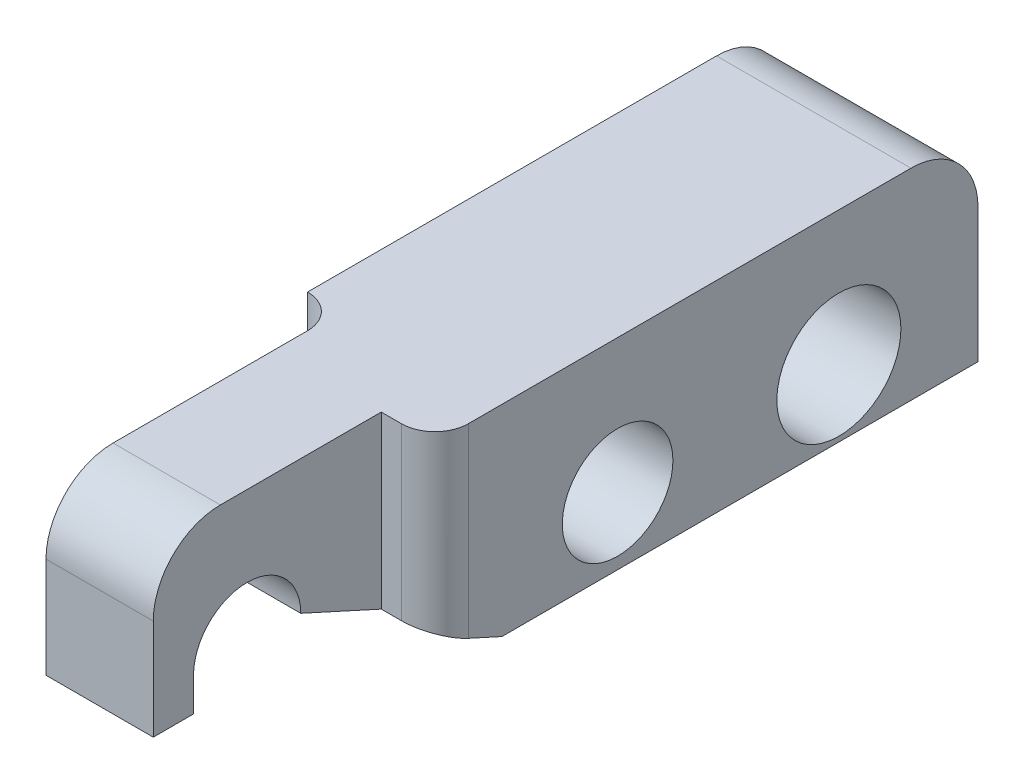
SolidWorks part; units mm, degrees
note: The reader was unsure of these and kept them because the rebuilt part matched: shared geometry of "草图1<11>".
ref_plane "前视基准面" through (0, 0, 0) normal (0, 0, 1) x (1, 0, 0)
ref_plane "上视基准面" through (0, 0, 0) normal (0, 1, 0) x (1, 0, 0)
ref_plane "右视基准面" through (0, 0, 0) normal (1, 0, 0) x (0, 0, -1)
other "Configuration Table"
sketch "草图1" plane through (0, 0, 0) normal (1, 0, 0) x (0, 0, -1)
  line L0 (-9.425, 0) -> (2.075, 0)
  line L21 (-9.425, 1) -> (2.075, 1)
  line L22 (-9.425, 1) -> (-9.425, -2)
  line L23 (-9.425, -2) -> (2.075, -2)
  line L24 (2.075, 1) -> (2.075, -2)
  line L25 (-8.825, 5.2785) -> (-8.825, 3.4146)
  line L26 (-0.925, 5.2633) -> (-0.925, 3.6744)
  line L27 (-7.225, 1) -> (-7.225, -2)
  line L28 (-7.225, 0) -> (-5.025, 1)
  line L29 (-9.425, 0.5) -> (-8.825, 0.5)
  line L30 (-9.425, 0.5) -> (-9.425, 0)
  line L31 (-9.425, 0) -> (-8.825, 0)
  line L32 (-8.825, 0.5) -> (-8.825, 0)
  line L33 (-5.025, 1) -> (-5.025, 0)
  circle A0 centre (0, 0) radius 0.925
  circle A1 centre (-3.3, 0) radius 0.825
  circle A2 centre (-8.025, 0) radius 0.8
  dimension "D1" = 1.85
  dimension "D2" = 1.65
  dimension "D9" = 1.6
  dimension "D3" = 3.3
  dimension "D4" = 3
  dimension "D5" = 11.5
  dimension "D6" = 0.6
  dimension "D7" = 3
  dimension "D8" = 2
  dimension "D10" = 0.5
  dimension "D11" = 2.2
extrude "凸台-拉伸1" add sketch "草图1" along normal blind 2.9 contours L32 L29 L22 L0 | L27 L28 L21 | A2 | A1 | A0
extrude "切除-拉伸1" cut sketch "草图1<11>" along normal through all contours A2 L27 L21 L22 L0 | L27 L28 L21
sketch "草图1<11>" plane through (0, 0, 0) normal (1, 0, 0) x (0, 0, -1) same geometry as "草图1"
sketch "草图2" plane through (0, -2, 0) normal (0, -1, 0) x (1, 0, 0)
  line L1 (0, 9.425) -> (2.9, 9.425)
  line L2 (0, 9.425) -> (0, 5.025)
  line L3 (0, 5.025) -> (2.9, 5.025)
  line L4 (2.9, 9.425) -> (2.9, 5.025)
  line L5 (2.9, 9.425) -> (0, 9.425) construction
  line L9 (2.1, 6.025) -> (2.9, 6.025)
  line L10 (0.5, 9.425) -> (2.1, 9.425)
  line L11 (0.5, 9.425) -> (0.5, 5.025)
  line L12 (0.5, 5.025) -> (2.1, 5.025)
  line L13 (2.1, 9.425) -> (2.1, 5.025)
  line L14 (0, 9.425) -> (0, -2.075) construction
  line L15 (2.9, 9.425) -> (2.9, -2.075) construction
  dimension "D1" = 4.4
  dimension "D2" = 1.6
  dimension "D3" = 0.5
  dimension "D4" = 1
extrude "切除-拉伸2" cut sketch "草图2" against normal through all
fillet "圆角2" radius 1 2 edges at (1.3, -2, 9.425) (1.45, -2, -2.075)
fillet "圆角3" radius 0.5 2 edges at (2.9, -0.7273, 6.025) (0.5, -0.5, 5.025)
ref_plane "基准面1" through (0, 10, 0) normal (0, 1, 0) x (1, 0, 0)
mirror "镜向1" about plane through (0, 10, 0) normal (0, 1, 0) of bodies 133
sketch "草图3" plane through (0, 10, 0) normal (0, 1, 0) x (1, 0, 0)
  line L1 (-18.4406, 12.3611) -> (29.0028, 12.3611)
  line L2 (-18.4406, 12.3611) -> (-18.4406, -16.7917)
  line L3 (-18.4406, -16.7917) -> (29.0028, -16.7917)
  line L4 (29.0028, 12.3611) -> (29.0028, -16.7917)
extrude "切除-拉伸3" cut sketch "草图3" against normal through all
